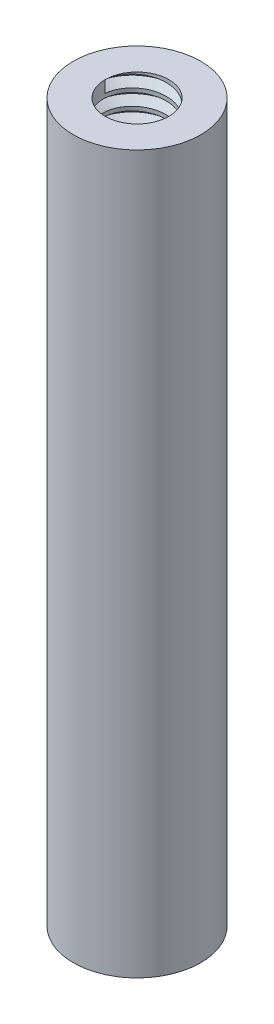
SolidWorks part; units mm, degrees
ref_plane "Front Plane" through (0, 0, 0) normal (0, 0, 1) x (1, 0, 0)
ref_plane "Top Plane" through (0, 0, 0) normal (0, 1, 0) x (1, 0, 0)
ref_plane "Right Plane" through (0, 0, 0) normal (1, 0, 0) x (0, 0, -1)
sketch "Sketch1" plane through (0, 0, 0) normal (0, 1, 0) x (1, 0, 0)
  circle A0 centre (0, 0) radius 3.175
  dimension "D1" = 6.35
extrude "Boss-Extrude1" add sketch "Sketch1" along normal blind 35.7251
ref_plane "Plane1" through (0, 6.35, 0) normal (0, -1, 0) x (-1, 0, 0)
sketch "Sketch3" plane through (0, 35.7251, 0) normal (0, 1, 0) x (1, 0, 0)
  circle A0 centre (0, 0) radius 1.5875
  dimension "D1" = 3.175
extrude "Cut-Extrude1" cut sketch "Sketch3" against normal blind 6.35
sketch "Sketch4" plane through (0, 0, 0) normal (0, -1, 0) x (1, 0, 0)
  circle A0 centre (0, 0) radius 1.5875
  dimension "D1" = 3.175
extrude "Cut-Extrude2" cut sketch "Sketch4" against normal blind 6.35
thread "Thread1" pitch 0.7937 method cut profile "Thread Profile2" start angle 0, offset 0, length 0, pitch 0.7937, diameter 3.175
ref_plane "Plane3" through (1.5875, 0, 0) normal (0, 0, 1) x (1, 0, 0)
sketch "Thread Profile2" plane through (1.5875, 0, 0) normal (0, 0, 1) x (1, 0, 0)
  line L0 (0, 0) -> (0, 0.7937) construction
  line L1 (0, 0) -> (0.4296, 0.248)
  line L2 (0.4296, 0.248) -> (0.4296, 0.3473)
  line L3 (0.4296, 0.3473) -> (0, 0.5953)
  line L4 (0.4296, 0.2977) -> (0, 0.2977) construction
  line L11 (0, 0) -> (0, 0.5953)
  point P2 (0, 0)
  dimension "Pitch" = 0.7937
  dimension "Profile_Angle" = 60
  dimension "Profile_Land" = 0.0992
  dimension "Profile_Height" = 0.4296
thread "Thread2" pitch 0.7937 method cut profile "Thread Profile3" start angle 0, offset 0, length 0, pitch 0.7937, diameter 3.175
ref_plane "Plane4" through (-1.5875, 35.7251, 0) normal (0, 0, 1) x (-1, 0, 0)
sketch "Thread Profile3" plane through (-1.5875, 35.7251, 0) normal (0, 0, 1) x (-1, 0, 0)
  line L0 (0, 0) -> (0, 0.7937) construction
  line L1 (0, 0) -> (0.4296, 0.248)
  line L2 (0.4296, 0.248) -> (0.4296, 0.3473)
  line L3 (0.4296, 0.3473) -> (0, 0.5953)
  line L4 (0.4296, 0.2977) -> (0, 0.2977) construction
  line L11 (0, 0) -> (0, 0.5953)
  point P2 (0, 0)
  dimension "Pitch" = 0.7937
  dimension "Profile_Angle" = 60
  dimension "Profile_Land" = 0.0992
  dimension "Profile_Height" = 0.4296
